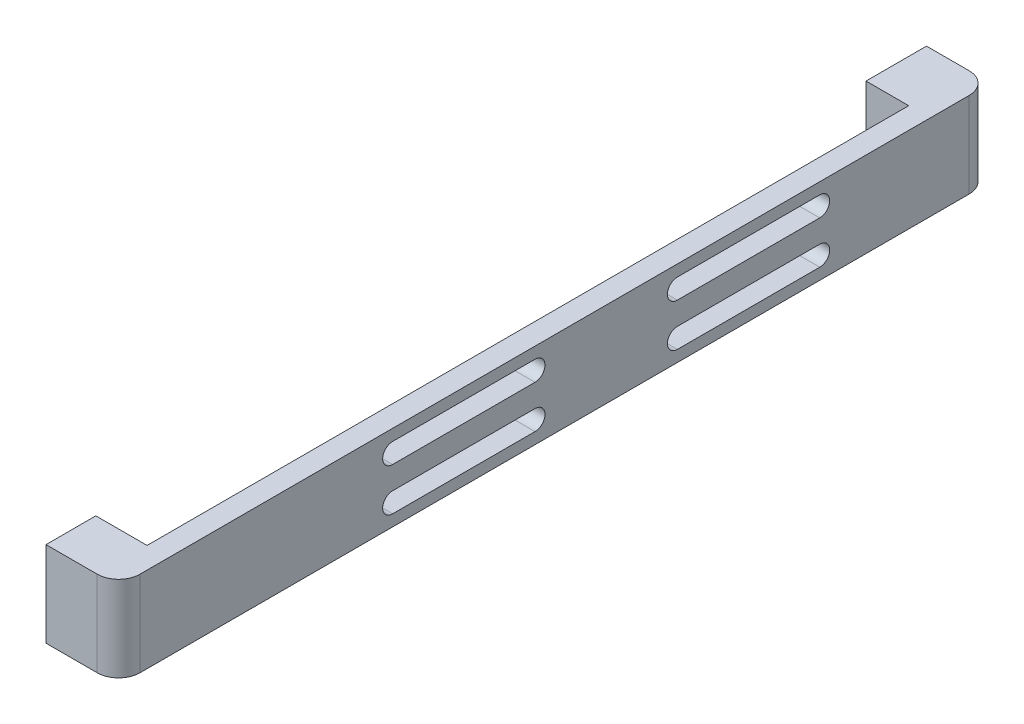
SolidWorks part; units mm, degrees
ref_plane "Front Plane" through (0, 0, 0) normal (0, 0, 1) x (1, 0, 0)
ref_plane "Top Plane" through (0, 0, 0) normal (0, 1, 0) x (1, 0, 0)
ref_plane "Right Plane" through (0, 0, 0) normal (1, 0, 0) x (0, 0, -1)
sketch "Sketch1" plane through (0, 0, 0) normal (1, 0, 0) x (0, 0, -1)
  line L1 (53.5, -6) -> (-53.5, -6)
  line L2 (53.5, -6) -> (53.5, 6)
  line L3 (53.5, 6) -> (-53.5, 6)
  line L4 (-53.5, -6) -> (-53.5, 6)
  line L5 (53.5, -6) -> (-53.5, 6) construction
  line L6 (53.5, 6) -> (-53.5, -6) construction
  line L7 (-53.5, 6) -> (-60.5, 6)
  line L8 (-53.5, 6) -> (-53.5, -6)
  line L9 (-53.5, -6) -> (-60.5, -6)
  line L10 (-60.5, 6) -> (-60.5, -6)
  line L11 (53.5, 6) -> (62, 6)
  line L12 (53.5, 6) -> (53.5, -6)
  line L13 (53.5, -6) -> (62, -6)
  line L14 (62, 6) -> (62, -6)
  point P0 (0, 0)
  dimension "D1" = 107
  dimension "D2" = 7
  dimension "D3" = 8.5
  dimension "D4" = 12
extrude "Boss-Extrude1" add sketch "Sketch1" along normal blind 5 contours L7 L10 L9 L4 | L14 L11 L2 L13 region at (0, 0, -57.75) region at (0, 0, 57)
sketch "Sketch3" plane through (5, 0, 0) normal (1, 0, 0) x (0, 0, -1)
  line L1 (-60.5, 6) -> (62, 6)
  line L2 (-60.5, 6) -> (-60.5, -6)
  line L3 (-60.5, -6) -> (62, -6)
  line L4 (62, 6) -> (62, -6)
extrude "Boss-Extrude2" add sketch "Sketch3" along normal blind 3
sketch "Sketch4" plane through (8, 0, 0) normal (1, 0, 0) x (0, 0, -1)
  line L0 (-60.5, 0) -> (62, 0) construction
  line L1 (-60.5, 6) -> (-60.5, -6) construction
  line L2 (62, -6) -> (62, 6) construction
  line L3 (0.75, 6) -> (0.75, -6) construction
  line L5 (-60.5, -6) -> (62, -6) construction
  line L6 (-22, 3) -> (-2, 3) construction
  line L7 (-12, -3) -> (28, -3) construction
  line L8 (-12, -3) -> (-12, 3) construction
  line L9 (-12, 3) -> (28, 3) construction
  line L10 (28, -3) -> (28, 3) construction
  line L11 (-12, -3) -> (28, 3) construction
  line L12 (-12, 3) -> (28, -3) construction
  line L13 (-22, 4.4) -> (-2, 4.4)
  line L14 (-22, 1.6) -> (-2, 1.6)
  line L15 (38, 3) -> (18, 3) construction
  line L16 (38, 1.6) -> (18, 1.6)
  line L17 (38, 4.4) -> (18, 4.4)
  line L18 (38, -3) -> (18, -3) construction
  line L19 (38, -4.4) -> (18, -4.4)
  line L20 (38, -1.6) -> (18, -1.6)
  line L21 (-22, -3) -> (-2, -3) construction
  line L22 (-22, -1.6) -> (-2, -1.6)
  line L23 (-22, -4.4) -> (-2, -4.4)
  line L24 (62, 6) -> (-60.5, 6) construction
  circle A0 centre (-12, 3) radius 1.4
  circle A1 centre (-12, -3) radius 1.4
  circle A2 centre (28, -3) radius 1.4
  circle A3 centre (28, 3) radius 1.4
  arc A4 (-22, 4.4) -> (-22, 1.6) centre (-22, 3) ccw
  arc A5 (-2, 1.6) -> (-2, 4.4) centre (-2, 3) ccw
  arc A6 (38, 1.6) -> (38, 4.4) centre (38, 3) ccw
  arc A7 (18, 4.4) -> (18, 1.6) centre (18, 3) ccw
  arc A8 (38, -4.4) -> (38, -1.6) centre (38, -3) ccw
  arc A9 (18, -1.6) -> (18, -4.4) centre (18, -3) ccw
  arc A10 (-22, -1.6) -> (-22, -4.4) centre (-22, -3) ccw
  arc A11 (-2, -4.4) -> (-2, -1.6) centre (-2, -3) ccw
  point P12 (0.75, 0)
  point P23 (-12, 3)
  point P29 (28, 3)
  point P36 (28, -3)
  point P43 (-12, -3)
  point P60 (8, 0)
  dimension "D1" = 2.8
  dimension "D2" = 40
  dimension "D3" = 6
  dimension "D4" = 20
  dimension "D5" = 8
extrude "Cut-Extrude1" cut sketch "Sketch4" against normal blind 3 contours L13 A4 L14 A0 | A0 | L14 A5 L13 A0 | L23 A11 L22 A1 | A1 | L22 A10 L23 A1 | L20 A9 L19 A2 | L17 A7 L16 A3 | A3 | L16 A6 L17 A3 | L19 A8 L20 A2 | A2 region at (8, 3, 18.0996) region at (8, 3, 5.9004) region at (8, 3, 12) region at (8, 3, -34.0996) region at (8, 3, -21.9004) region at (8, 3, -28) region at (8, -3, -34.0996) region at (8, -3, -21.9004) region at (8, -3, -28) region at (8, -3, 18.0996) region at (8, -3, 5.9004) region at (8, -3, 12)
fillet "Fillet1" radius 3 2 edges at (8, 0, -62) (8, 0, 60.5)
sketch "Sketch5" plane through (0, 0, 0) normal (-1, 0, 0) x (0, 0, 1)
  line L4 (60.5, 6) -> (53.5, 6)
  line L5 (53.5, 6) -> (53.5, -6)
  line L6 (53.5, -6) -> (60.5, -6)
  line L7 (60.5, -6) -> (60.5, 6)
  line L8 (60.5, 6) -> (53.5, 6)
  line L9 (53.5, 6) -> (53.5, -6)
  line L10 (53.5, -6) -> (60.5, -6)
  line L11 (60.5, -6) -> (60.5, 6)
  dimension "D1" = 0
extrude "Boss-Extrude3" add sketch "Sketch5" along normal blind 2.2
sketch "Sketch6" plane through (0, 0, 0) normal (-1, 0, 0) x (0, 0, 1)
  line L4 (-62, 6) -> (-62, -6)
  line L5 (-62, -6) -> (-53.5, -6)
  line L6 (-53.5, -6) -> (-53.5, 6)
  line L7 (-53.5, 6) -> (-62, 6)
  line L8 (-62, 6) -> (-62, -6)
  line L9 (-62, -6) -> (-53.5, -6)
  line L10 (-53.5, -6) -> (-53.5, 6)
  line L11 (-53.5, 6) -> (-62, 6)
  dimension "D1" = 0
extrude "Boss-Extrude4" add sketch "Sketch6" along normal blind 1
